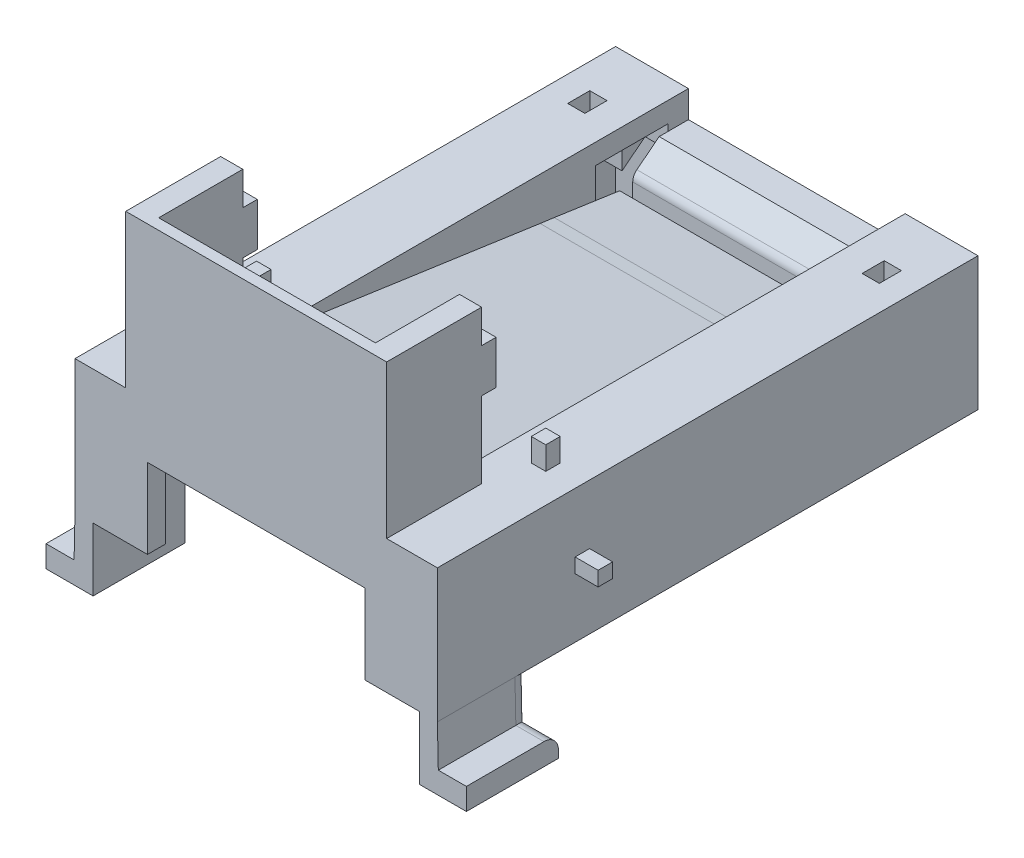
SolidWorks part; units mm, degrees
ref_plane "Front Plane" through (0, 0, 0) normal (0, 0, 1) x (1, 0, 0)
ref_plane "Top Plane" through (0, 0, 0) normal (0, 1, 0) x (1, 0, 0)
ref_plane "Right Plane" through (0, 0, 0) normal (1, 0, 0) x (0, 0, -1)
sketch "Sketch1" plane through (0, 0, 0) normal (0, 0, 1) x (1, 0, 0)
  line L1 (-25, 9.2) -> (25, 9.2)
  line L2 (-25, 9.2) -> (-25, -9.2)
  line L3 (-25, -9.2) -> (25, -9.2)
  line L4 (25, 9.2) -> (25, -9.2)
  line L5 (-25, 9.2) -> (25, -9.2) construction
  line L6 (-25, -9.2) -> (25, 9.2) construction
  point P0 (0, 0)
  dimension "D1" = 50
  dimension "D2" = 18.4
extrude "Boss-Extrude1" add sketch "Sketch1" along normal blind 78
sketch "Sketch2" plane through (0, -9.2, 0) normal (0, -1, 0) x (-1, 0, 0)
  line L0 (-25, -78) -> (-25, 0) construction
  line L1 (-22.5, -14.6) -> (-14.95, -14.6)
  line L2 (-22.5, -14.6) -> (-22.5, -9.4)
  line L3 (-22.5, -9.4) -> (-14.95, -9.4)
  line L4 (-14.95, -14.6) -> (-14.95, -9.4)
  line L5 (25, 0) -> (-25, 0) construction
  line L6 (22.5, -14.6) -> (14.95, -14.6)
  line L7 (22.5, -14.6) -> (22.5, -9.4)
  line L8 (22.5, -9.4) -> (14.95, -9.4)
  line L9 (14.95, -14.6) -> (14.95, -9.4)
  line L10 (-22.5, -12) -> (-25, -12) construction
  line L11 (14.95, -12.9) -> (-14.95, -12.9)
  line L12 (14.95, -12.9) -> (14.95, -11.1)
  line L13 (14.95, -11.1) -> (-14.95, -11.1)
  line L14 (-14.95, -12.9) -> (-14.95, -11.1)
  line L15 (22.5, -12) -> (25, -12) construction
  line L19 (25, -78) -> (25, 0) construction
  point P12 (14.95, -12)
  point P13 (-14.95, -12)
  point P15 (14.95, -12)
  line M14 (-25, 0) -> (-25, -78)
  line M16 (25, -78) -> (25, 0)
  dimension "D1" = 5.2
  dimension "D2" = 7.55
  dimension "D3" = 1.8
  dimension "D4" = 2.5
  dimension "IRdist" = 12
extrude "Cut-Extrude1" cut sketch "Sketch2" against normal blind 15.6 contours L9 L6 L8 M16 | L9 L13 L4 L11 | L1 L4 L3 M14 region at (18.725, -9.2, 12) region at (0, -9.2, 12) region at (-18.725, -9.2, 12)
sketch "Sketch3" plane through (0, 0, 0) normal (1, 0, 0) x (0, 0, -1)
  line L0 (-2.5, -9.2) -> (-2.5, 6.2)
  line L1 (-78, -9.2) -> (0, -9.2) construction
  line L2 (-2.5, 6.2) -> (-11.798, -1.1232)
  line L3 (-11.798, -1.1232) -> (-75.5, 6.2)
  line L4 (-75.5, 6.2) -> (-75.5, -9.2)
  line L5 (-75.5, -9.2) -> (-2.5, -9.2)
  line L6 (-78, 9.2) -> (0, 9.2) construction
  line L7 (-78, 9.2) -> (0, 9.2) construction
  line L8 (-78, 9.2) -> (-78, -9.2) construction
  line L9 (-2.7315, 9.2) -> (-12, 1.9)
  line L10 (-12, 1.9) -> (-75.5, 9.2)
  line L11 (-75.5, 9.2) -> (-2.7315, 9.2)
  line L12 (-14.6, 6.4) -> (-9.4, 6.4) construction
  line L13 (0, 9.2) -> (0, -9.2) construction
  line L14 (-21.9346, 3.0421) -> (-12, 1.6)
  line L15 (-12, 1.6) -> (-12, 1.9)
  dimension "D1" = 2.5
  dimension "D3" = 2.5
  dimension "D4" = 4.5
  dimension "D2" = 3
  dimension "D5" = 2.5
  dimension "D6" = 12
  dimension "D7" = 0.3
  dimension "D8" = 10
extrude "Cut-Extrude2" cut sketch "Sketch3" against normal up to vertex (22.5 mm away) contours L4 L5 L0 L2 L3 region at (0, -3.1404, 41.8284) up to point (-22.5, -9.2, 14.6)
mirror "Mirror3" about plane through (0, 0, 0) normal (1, 0, 0) of "Cut-Extrude2"
extrude "Cut-Extrude3" cut sketch "Sketch3<3>" against normal up to vertex (14.95 mm away) contours L11 L10 L9 | L14 L15 L10 region at (0, 6.7667, 30.0772) region at (0, 2.1807, 15.3115) up to point (-14.95, -0.9965, 12.9)
sketch "Sketch3<3>" plane through (0, 0, 0) normal (1, 0, 0) x (0, 0, -1) same geometry as "Sketch3"
mirror "Mirror4" about plane through (0, 0, 0) normal (1, 0, 0) of "Cut-Extrude3"
sketch "Sketch12" plane through (22.5, 0, 0) normal (-1, 0, 0) x (0, 0, 1)
  line L0 (9.4, 6.4) -> (9.4, 0.7655)
  line L1 (9.4, 0.7655) -> (9.475, 6.4)
  line L3 (9.475, 6.4) -> (9.4, 6.4)
  line L4 (14.6, 6.4) -> (14.6, -0.8011)
  line L5 (14.6, -0.8011) -> (14.525, 6.4)
  line L6 (14.525, 6.4) -> (14.6, 6.4)
  dimension "D1" = 5.05
extrude "Boss-Extrude3" add sketch "Sketch12" along normal up to surface (7.55 mm away) up to face at (14.95, 5.7382, 21.1666)
extrude "Boss-Extrude4" add sketch "Sketch12<2>" against normal up to surface (-37.45 mm away) from surface up to face at (-14.95, 1.6872, 10.25) starting at face at (-22.5, 0.8455, 25.5)
sketch "Sketch12<2>" plane through (22.5, 0, 0) normal (-1, 0, 0) x (0, 0, 1) same geometry as "Sketch12"
sketch "Sketch31" plane through (0, -9.2, 0) normal (0, -1, 0) x (1, 0, 0)
  line L1 (-14.95, 9.475) -> (-18.125, 9.475)
  line L2 (-14.95, 9.475) -> (-14.95, 6.225)
  line L3 (-14.95, 6.225) -> (-18.125, 6.225)
  line L4 (-18.125, 9.475) -> (-18.125, 6.225)
  line L5 (18.125, 9.475) -> (14.95, 9.475)
  line L6 (18.125, 9.475) -> (18.125, 6.225)
  line L7 (18.125, 6.225) -> (14.95, 6.225)
  line L8 (14.95, 9.475) -> (14.95, 6.225)
  line L9 (-14.95, 14.6) -> (-14.95, 12.9) construction
  line L14 (-14.95, 14.525) -> (-18.125, 14.525)
  line L15 (-14.95, 14.525) -> (-14.95, 16.225)
  line L16 (-14.95, 16.225) -> (-18.125, 16.225)
  line L17 (-18.125, 14.525) -> (-18.125, 16.225)
  line L18 (-14.95, 14.525) -> (-22.5, 14.525) construction
  line L19 (14.95, 14.6) -> (22.5, 14.6) construction
  line L20 (14.95, 14.525) -> (18.125, 14.525)
  line L21 (14.95, 14.525) -> (14.95, 16.225)
  line L22 (14.95, 16.225) -> (18.125, 16.225)
  line L23 (18.125, 14.525) -> (18.125, 16.225)
  dimension "D2" = 3.175
  dimension "D1" = 10
  dimension "D3" = 8.375
extrude "Cut-Extrude4" cut sketch "Sketch31" against normal up to surface (15.6 mm away) up to face at (-18.725, 6.4, 12)
sketch "Sketch17" plane through (-14.95, 0, 0) normal (1, 0, 0) x (0, 0, -1)
  line L0 (-78, 9.2) -> (-78, 10.7)
  line L1 (-78, 10.7) -> (-21.9346, 3.0421)
  line L2 (-21.9346, 3.0421) -> (-75.5, 9.2)
  line L3 (-75.5, 9.2) -> (-78, 9.2)
  dimension "D1" = 1.5
extrude "Boss-Extrude7" add sketch "Sketch17" along normal up to surface (29.9 mm away) up to face at (14.95, 6.0759, 23.1504)
sketch "Sketch18" plane through (14.95, 0, 0) normal (1, 0, 0) x (0, 0, -1)
  line L0 (-78, 10.7) -> (-78, 9.2)
  line L1 (-78, 9.2) -> (-67.0181, 9.2)
  line L2 (-78, 9.2) -> (-67.0181, 9.2) construction
  line L4 (-67.0181, 9.2) -> (-78, 10.7)
  line L5 (-78, 10.7) -> (-67.0181, 9.2) construction
extrude "Mtrl Rmv" cut sketch "Sketch18" against normal through all
ref_plane "Plane4" through (0, 0, 65.75) normal (0, 0, 1) x (1, 0, 0)
ref_plane "Plane5" through (18, 0, 0) normal (1, 0, 0) x (0, 0, -1)
sketch "Sketch25" plane through (0, 0, 0) normal (1, 0, 0) x (0, 0, -1)
  line L0 (-78, -9.2) -> (0, -9.2) construction
  line L1 (-78, 9.2) -> (-76.5, 9.2)
  line L2 (-78, 9.2) -> (-78, 30.3)
  line L3 (-78, 30.3) -> (-76.5, 30.3)
  line L4 (-76.5, 9.2) -> (-76.5, 30.3)
  line L5 (-70.7642, 18.6552) -> (-76.5, 23.3)
  line L6 (-70.7642, 18.6552) -> (-76.5, 18.6552)
  line L10 (-76.5, 10.4951) -> (-67.0181, 9.2)
  line L11 (-78, 9.2) -> (0, 9.2) construction
  line L12 (-21.9346, 3.0421) -> (-67.0181, 9.2) construction
  line L13 (-67.0181, 9.2) -> (-76.5, 9.2)
  dimension "D1" = 1.5
  dimension "D2" = 39.5
  dimension "D3" = 9.4552
  dimension "D4" = 51
  dimension "D5" = 7
extrude "Boss-Extrude9" add sketch "Sketch25" against normal mid plane 36 contours L1 L4 L3 L2 | L6 L5 L4 | L13 L10 L4 region at (0, 19.75, 77.25) region at (0, 9.6317, 73.3394) region at (0, 20.2035, 74.5881)
sketch "Sketch27" plane through (0, 0, 78) normal (0, 0, 1) x (1, 0, 0)
  line L0 (-18, 30.3) -> (18, 30.3) construction
  line L1 (-18, 9.2) -> (-14.95, 9.2)
  line L2 (-18, 9.2) -> (-18, 30.3)
  line L3 (-18, 30.3) -> (-14.95, 30.3)
  line L4 (-14.95, 9.2) -> (-14.95, 30.3)
  line L5 (25, 9.2) -> (18, 9.2) construction
  line L6 (18, 9.2) -> (14.95, 9.2)
  line L7 (18, 9.2) -> (18, 30.3)
  line L8 (18, 30.3) -> (14.95, 30.3)
  line L9 (14.95, 9.2) -> (14.95, 30.3)
  line L10 (-18, 9.2) -> (-25, 9.2) construction
extrude "Boss-Extrude10" add sketch "Sketch27" against normal blind 13.1
sketch "Sketch30" plane through (18, 0, 0) normal (1, 0, 0) x (0, 0, -1)
  line L0 (-64.9, 9.2) -> (-64.9, 30.3) construction
  line L1 (-64.9, 25.7) -> (-62.9, 25.7)
  line L2 (-64.9, 25.7) -> (-64.9, 19.7)
  line L3 (-64.9, 19.7) -> (-62.9, 19.7)
  line L4 (-62.9, 25.7) -> (-62.9, 19.7)
  line L5 (-78, 9.2) -> (-64.9, 9.2) construction
  dimension "D1" = 2
  dimension "D2" = 6
  dimension "D3" = 10.5
extrude "Boss-Extrude11" add sketch "Sketch30" against normal up to surface (3.05 mm away) up to face at (14.95, 14.0134, 47.4972)
extrude "Boss-Extrude12" add sketch "Sketch30<2>" along normal up to surface (-32.95 mm away) from surface up to face at (-14.95, 14.0134, 47.4972) starting at face at (-18, 19.75, 71.45)
sketch "Sketch30<2>" plane through (18, 0, 0) normal (1, 0, 0) x (0, 0, -1) same geometry as "Sketch30"
sketch "Sketch32" plane through (0, 0, 0) normal (1, 0, 0) x (0, 0, -1)
  line L1 (-3.4133, 5.4806) -> (-3.4133, 8.6629)
  line L2 (-2.7315, 9.2) -> (-6.2865, 6.4) construction
  line L3 (-5.9133, 3.5116) -> (-5.9133, 6.6939)
  line L4 (-5.9133, 6.6939) -> (-3.4133, 8.6629)
  line L9 (-5.9133, 3.5116) -> (-5.9133, -9.2)
  line L10 (-2.5, 6.2) -> (-9.4, 0.7655) construction
  line L11 (-75.5, -9.2) -> (-2.5, -9.2) construction
  line L13 (-5.9133, -9.2) -> (-3.4133, -9.2)
  line L14 (-3.4133, -9.2) -> (-3.4133, 5.4806)
  line L15 (-3.4133, 5.4806) -> (-5.9133, 3.5116)
  line L16 (-3.4133, 5.4806) -> (-7.4538, 5.4806) construction
  line L17 (-6.2865, 6.4) -> (-11.1, 2.6089) construction
  line L18 (-7.4538, 5.4806) -> (-12.7591, 5.4806) construction
  circle A0 centre (-12.7591, 3.7257) radius 2 construction
  dimension "D2" = 4
  dimension "D1" = 2.5
  dimension "D3" = 3.75
extrude "Shorter Front Lip" add sketch "Sketch32" along normal mid plane 45 contours L14 L15 L9 L13 | L15 L1 L4 L3 region at (0, 6.0873, 4.6633) region at (0, -2.3401, 4.6334)
sketch "Sketch33" plane through (0, 0, 0) normal (1, 0, 0) x (0, 0, -1)
  line L1 (0, -9.2) -> (-3.4133, -9.2)
  line L2 (0, -9.2) -> (0, 9.2)
  line L3 (0, 9.2) -> (-3.4133, 9.2)
  line L4 (-3.4133, -9.2) -> (-3.4133, 9.2)
  line L5 (-3.4133, -9.2) -> (-3.4133, 5.4806) construction
  line L6 (-64.9, 9.2) -> (-2.7315, 9.2) construction
  line L8 (-9.475, 6.4) -> (-9.475, 7.9) construction
  line L9 (-64.9, 9.2) -> (-3.4133, 9.2)
  line L11 (-3.4133, 5.4806) -> (-7.4538, 5.4806)
  line L12 (-7.4538, 5.4806) -> (-7.4538, 9.2)
  dimension "D1" = 1.5
extrude "Shorter Front Cut" cut sketch "Sketch33" against normal through all both and the other way through all contours L4 L1 L2 L3 | L12 region at (0, 0, 1.7067)
extrude "Cut-Extrude7" cut sketch "Sketch33<3>" against normal mid plane 29.9 contours L12 L11 region at (0, 7.3403, 5.4336)
sketch "Sketch33<3>" plane through (0, 0, 0) normal (1, 0, 0) x (0, 0, -1) same geometry as "Sketch33"
sketch "Sketch13" plane through (0, 0, 0) normal (0, 0, 1) x (1, 0, 0)
  line L0 (15, 0) -> (-15, 0) construction
  line L1 (13, 1) -> (15, 1)
  line L2 (13, 1) -> (13, -1)
  line L3 (13, -1) -> (15, -1)
  line L4 (15, 1) -> (15, -1)
  line L5 (-15, 1) -> (-13, 1)
  line L6 (-15, 1) -> (-15, -1)
  line L7 (-15, -1) -> (-13, -1)
  line L8 (-13, 1) -> (-13, -1)
  point P9 (14, -1)
  point P16 (0, 0)
  dimension "D1" = 2
  dimension "D2" = 8.5
sketch "Sketch34" plane through (14.95, 0, 0) normal (-1, 0, 0) x (0, 0, 1)
  line L0 (12.9, 1.7306) -> (64.9, 9.2)
  line L1 (76.5, 10.4951) -> (76.5, 18.6552) construction
  line L2 (12.9, 1.7306) -> (76.5, 10.4951)
  line L3 (76.5, 10.4951) -> (21.9346, 3.0421) construction
  line L4 (76.5, 17.6552) -> (76.5, 10.4951)
  line L9 (76.5, 17.6552) -> (64.9, 9.2)
  line L11 (78, 9.2) -> (3.4133, 9.2) construction
  point P17 (67.4, 13.98)
  dimension "D1" = 5.72
  dimension "D2" = 4.5
  dimension "D4" = 1
extrude "Boss-Extrude13" add sketch "Sketch34" along normal up to surface (29.9 mm away) up to face at (-14.95, 14.9957, 46.4347)
extrude "Front Shield Pegs (72/78)" add sketch "Sketch13<2>" against normal blind 3.175 from surface starting at face at (0, 3.6702, 3.4133)
sketch "Sketch13<2>" plane through (0, 0, 0) normal (0, 0, 1) x (1, 0, 0) same geometry as "Sketch13"
fillet "Fillet11" [suppressed] radius 6
sketch "Sketch4" plane through (0, 0, 78) normal (0, 0, 1) x (1, 0, 0)
  line L0 (-25, -9.2) -> (25, -9.2) construction
  line L1 (-15, -9.2) -> (15, -9.2)
  line L2 (-15, -9.2) -> (-15, 1.8)
  line L3 (-15, 1.8) -> (15, 1.8)
  line L4 (15, -9.2) -> (15, 1.8)
  point P6 (0, 1.8)
  dimension "D1" = 30
  dimension "D2" = 11
extrude "Wire Hole" cut sketch "Sketch4" against normal up to surface (2.5 mm away) up to face at (0, -1.5, 75.5)
extrude "Front Shield Pegs" [suppressed] add sketch "Sketch13" against normal blind 3.175 from surface starting at face at (14, 0, 3.4133)
sketch "Sketch14" plane through (0, 9.2, 0) normal (0, 1, 0) x (1, 0, 0)
  line L0 (18.95, -58) -> (-18.95, -58) construction
  line L1 (20.95, -57) -> (18.95, -57)
  line L2 (20.95, -57) -> (20.95, -59)
  line L3 (20.95, -59) -> (18.95, -59)
  line L4 (18.95, -57) -> (18.95, -59)
  line L5 (-18.95, -57) -> (-20.95, -57)
  line L6 (-18.95, -57) -> (-18.95, -59)
  line L7 (-18.95, -59) -> (-20.95, -59)
  line L8 (-20.95, -57) -> (-20.95, -59)
  line L9 (14.95, -64.9) -> (14.95, -3.4133) construction
  line L10 (25, -78) -> (18, -78) construction
  point P8 (0, -58)
  point P12 (20.95, -58)
  point P15 (19.95, -57)
  dimension "D1" = 2
  dimension "D2" = 20
  dimension "D3" = 5
extrude "Top Shield Pegs" add sketch "Sketch14" along normal blind 3.175
fillet "Fillet9" [suppressed] radius 10
fillet "Fillet10" radius 1.5 1 edges at (0, 2.6089, 11.1)
ref_plane "Plane3" through (0, 0, 54) normal (0, 0, 1) x (1, 0, 0)
sketch "Sketch19" plane through (0, 0, 54) normal (0, 0, 1) x (1, 0, 0)
  line L0 (22.5, -9.2) -> (22.5, -17.915)
  line L1 (22.5, -17.915) -> (29, -17.915)
  line L2 (29, -17.915) -> (29, -14.915)
  line L3 (29, -14.915) -> (25, -14.915)
  line L4 (25, -14.915) -> (25, -9.2)
  line L5 (25, -9.2) -> (22.5, -9.2)
  line L6 (-22.5, -9.2) -> (-22.5, -17.915)
  line L7 (-22.5, -17.915) -> (-29, -17.915)
  line L8 (-29, -17.915) -> (-29, -14.915)
  line L9 (-29, -14.915) -> (-25, -14.915)
  line L10 (-25, -14.915) -> (-25, -9.2)
  line L11 (-25, -9.2) -> (-22.5, -9.2)
  dimension "D1" = 4
  dimension "D2" = 5.715
  dimension "D3" = 3
extrude "Legs" add sketch "Sketch19" against normal blind 12.7 from surface starting at face at (0, 5.35, 78)
sketch "Sketch35" plane through (0, 0, 78) normal (0, 0, 1) x (1, 0, 0)
  line L0 (-25, -14.915) -> (-25, -9.2)
  line L1 (-25, 9.2) -> (-25, -14.915) construction
  line L2 (-25, -9.2) -> (-25.125, -14.915)
  line L3 (-29, -14.915) -> (-25, -14.915) construction
  line L4 (-25.125, -14.915) -> (-25, -14.915)
  line L5 (25, -9.2) -> (25.125, -14.915)
  line L6 (25, -14.915) -> (25, 9.2) construction
  line L7 (25, -14.915) -> (29, -14.915) construction
  line L8 (25.125, -14.915) -> (25, -14.915)
  line L9 (25, -14.915) -> (25, -9.2)
  dimension "D1" = 0.125
extrude "Boss-Extrude14" add sketch "Sketch35" against normal up to surface (12.7 mm away) up to face at (-25.5, -14.01, 65.3)
sketch "Sketch29" plane through (-25, 0, 0) normal (-1, 0, 0) x (0, 0, 1)
  line L0 (58, 1) -> (58, 12.375) construction
  line L1 (57, 1) -> (59, 1)
  line L2 (57, 1) -> (57, -1)
  line L3 (57, -1) -> (59, -1)
  line L4 (59, 1) -> (59, -1)
  line L5 (57, 12.375) -> (59, 12.375) construction
  line L6 (40.7067, 9.2) -> (40.7067, -9.2) construction
  line L7 (57, 12.375) -> (57, 9.2) construction
  line L8 (57, 0) -> (40.7067, 0) construction
  line L10 (78, 9.2) -> (3.4133, 9.2) construction
  line L11 (65.3, -9.2) -> (3.4133, -9.2) construction
extrude "Side Shield Pegs1" add sketch "Sketch29" along normal blind 3.175
extrude "Side Shield Pegs2" add sketch "Sketch29<2>" against normal blind 3.175 from surface starting at face at (25, -1.84, 45.6253)
sketch "Sketch29<2>" plane through (-25, 0, 0) normal (-1, 0, 0) x (0, 0, 1) same geometry as "Sketch29"
fillet "Fillet12" radius 2 4 edges at (27.0625, -14.915, 65.3) (25.0625, -12.0575, 65.3) (-27.0625, -14.915, 65.3) (-25.0625, -12.0575, 65.3)
fillet "Fillet3" [suppressed] radius 3
fillet "Fillet5" [suppressed] radius 3
fillet "Fillet6" [suppressed] radius 3 tangent propagation no
sketch "Sketch5" [suppressed] plane through (0, 0, 0) normal (1, 0, 0) x (0, 0, -1)
  line L0 (-72, 3.5229) -> (-93, 15.1419)
  line L1 (-77.2, 16.8) -> (-77.2, 18.347)
  line L2 (-93, 15.1419) -> (-93, 22.3)
  line L3 (-93, 22.3) -> (-77.2, 22.3)
  line L5 (-77.2, 16.8) -> (-72, 13.9229)
  line L6 (-72, 13.9229) -> (-72, 3.5229)
  line L7 (-72, 9.2) -> (-72, -14.9531) construction
  line L8 (-77.2, 18.347) -> (-77.2, 22.3)
  line L10 (-3.717, 9.2) -> (-72, 9.2) construction
  line L11 (-77.2, 22.3) -> (-93, 22.3)
  line L12 (-77.2, 22.3) -> (-77.2, 30.675)
  line L13 (-77.2, 30.675) -> (-93, 30.675)
  line L14 (-93, 22.3) -> (-93, 30.675)
  line L19 (-72, 13.9229) -> (-35.4398, -6.3052)
  line L20 (-35.4398, -6.3052) -> (-35.4398, 9.2)
  line L22 (-35.4398, 9.2) -> (-72, 9.2)
  dimension "D1" = 24
  dimension "D2" = 21
  dimension "D3" = 13.1
  dimension "D4" = 5.2
  dimension "D5" = 5.5
  dimension "D6" = 10.4
  dimension "D7" = 8.375
extrude "Ramp Extrude" [suppressed] add sketch "Sketch5" along normal mid plane 15
ref_plane "Plane2" [suppressed] through (0, 9.7505, -1.4681) normal (0, 0.9889, -0.1489) x (1, 0, 0)
sketch "Sketch7" [suppressed] plane through (0, 0, 0) normal (1, 0, 0) x (0, 0, -1)
  line L1 (-93, 15.1419) -> (-93, 30.675) construction
  line L2 (-92, 19.3) -> (-92, 22.3)
  line L3 (-92, 22.3) -> (-77.2, 22.3)
  line L4 (-92, 22.3) -> (-77.2, 22.3)
  line L5 (-77.2, 22.3) -> (-77.2, 16.8)
  line L8 (-92, 22.3) -> (-92, 30.675)
  line L9 (-35.4398, 9.74) -> (-35.4398, 9.2)
  line L10 (-77.2, 27.675) -> (-92, 27.675) construction
  line L11 (-92, 30.675) -> (-77.2, 30.675)
  line L12 (-77.2, 22.3) -> (-77.2, 30.675)
  line L13 (-77.2, 30.675) -> (-93, 30.675) construction
  line L14 (-77.2, 16.8) -> (-77.2, 30.675) construction
  line L17 (-77.2, 16.8) -> (-35.4398, 9.74)
  line L21 (-35.4398, 9.2) -> (-83.2585, 17.3233)
  arc A0 (-92, 27.675) -> (-83.2585, 17.3233) centre (-81.5, 27.675) ccw
  dimension "D5" = 10.5
  dimension "D1" = 1
  dimension "D2" = 3
  dimension "D3" = 5.5
  dimension "D4" = 3
extrude "Ramp Shell Cut" [suppressed] cut sketch "Sketch7" against normal mid plane 13
sketch "Sketch8" [suppressed] plane through (-7.5, 0, 0) normal (-1, 0, 0) x (0, 0, 1)
  line L0 (77.2, 23.7375) -> (81.15, 30.675)
  line L1 (77.2, 16.8) -> (77.2, 30.675) construction
  line L2 (77.2, 30.675) -> (93, 30.675) construction
  line L3 (81.15, 30.675) -> (77.2, 30.675)
  line L4 (77.2, 30.675) -> (77.2, 23.7375)
  line L5 (77.2, 23.7375) -> (85.1, 23.7375) construction
  point P9 (85.1, 30.675)
  point P12 (81.15, 23.7375)
extrude "Ramp Corner Cuts" [suppressed] cut sketch "Sketch8" against normal through all
sketch "Sketch36" plane through (0, 9.2, 0) normal (0, 1, 0) x (1, 0, 0)
  line L0 (-21.5, -12) -> (21.5, -12) construction
  line L1 (-21.5, -13.525) -> (-19.125, -13.525)
  line L2 (-21.5, -13.525) -> (-21.5, -10.475)
  line L3 (-21.5, -10.475) -> (-19.125, -10.475)
  line L4 (-19.125, -13.525) -> (-19.125, -10.475)
  line L5 (19.125, -13.525) -> (21.5, -13.525)
  line L6 (19.125, -13.525) -> (19.125, -10.475)
  line L7 (19.125, -10.475) -> (21.5, -10.475)
  line L8 (21.5, -13.525) -> (21.5, -10.475)
  line L9 (-20.3125, -14.525) -> (-20.3125, -9.475) construction
  line L10 (-18.125, -14.525) -> (-22.5, -14.525) construction
  line L11 (-18.125, -9.475) -> (-22.5, -9.475) construction
  line L12 (-22.5, -14.525) -> (-22.5, -9.475) construction
  line L13 (-18.125, -14.6) -> (-18.125, -16.225) construction
  line L14 (0, -12) -> (0, 0) construction
  point P17 (-20.3125, -12)
  dimension "D1" = 1
  dimension "D2" = 1
  dimension "D3" = 1
extrude "Cut-Extrude8" cut sketch "Sketch36" against normal through all
equation "\"bottomThickness\"= .220in"
equation "\"wallThickness\"= .125in"
equation "\"D1@Front Shield Pegs\" = \"wallThickness\""
equation "\"D1@Top Shield Pegs\" = \"wallThickness\""
equation "\"IRdist\"=12"
equation "\"IRdist@Sketch2\"=\"IRdist\""
equation "\"D6@Sketch3\"=\"IRdist\""
equation "\"D1@Side Shield Pegs1\" = \"wallThickness\""
equation "\"D1@Side Shield Pegs2\" = \"wallThickness\""
equation "\"D2@Sketch19\"=\"bottomThickness\"+.005in"
equation "\"D2@Sketch31\"=\"wallThickness\""
equation "\"D1@Front Shield Pegs (72/78)\" = \"wallThickness\""
